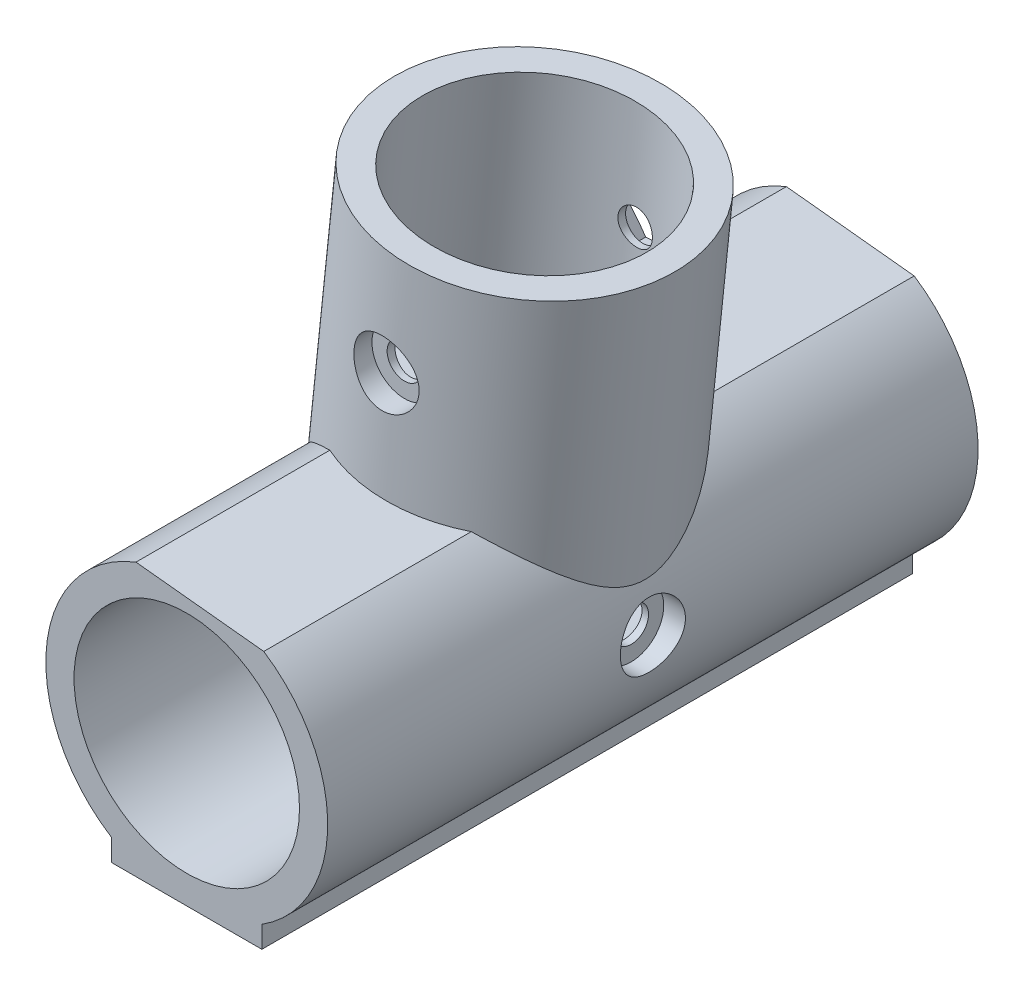
SolidWorks part; units mm, degrees
ref_plane "Front Plane" through (0, 0, 0) normal (0, 0, 1) x (1, 0, 0)
ref_plane "Top Plane" through (0, 0, 0) normal (0, 1, 0) x (1, 0, 0)
ref_plane "Right Plane" through (0, 0, 0) normal (1, 0, 0) x (0, 0, -1)
sketch "Sketch1" plane through (0, 0, 0) normal (0, 0, 1) x (1, 0, 0)
  line L0 (-13, 13) -> (13, -13) construction
  line L1 (-13, 13) -> (13, 13)
  line L2 (-13, 13) -> (-13, -13)
  line L3 (-13, -13) -> (13, -13)
  line L4 (13, 13) -> (13, -13)
  circle A0 centre (0, 0) radius 10.4
  point P4 (0, 0)
  dimension "D2" = 20.8
  dimension "D1" = 26
extrude "Boss-Extrude2" add sketch "Sketch1" along normal blind 60
sketch "Sketch2" plane through (-13, 0, 0) normal (-1, 0, 0) x (0, 0, 1)
  line L0 (0, 13) -> (60, -13) construction
  circle A0 centre (30, 0) radius 1.6
  point P4 (30, 0)
  dimension "D1" = 3.2
extrude "Cut-Extrude1" cut sketch "Sketch2" against normal through all
sketch "Sketch3" plane through (-13, 0, 0) normal (-1, 0, 0) x (0, 0, 1)
  line L1 (33.3486, 0) -> (31.6743, 2.9)
  line L2 (31.6743, 2.9) -> (28.3257, 2.9)
  line L3 (28.3257, 2.9) -> (26.6514, 0)
  line L4 (26.6514, 0) -> (28.3257, -2.9)
  line L5 (28.3257, -2.9) -> (31.6743, -2.9)
  line L6 (31.6743, -2.9) -> (33.3486, 0)
  circle A0 centre (30, 0) radius 2.9 construction
  dimension "D1" = 5.8
extrude "Cut-Extrude2" cut sketch "Sketch3" against normal blind 2
sketch "Sketch4" plane through (13, 0, 0) normal (1, 0, 0) x (0, 0, -1)
  circle A0 centre (-30, 0) radius 3
  dimension "D1" = 6
extrude "Cut-Extrude3" cut sketch "Sketch4" against normal blind 2
sketch "Sketch6" plane through (0, 0, 60) normal (0, 0, 1) x (1, 0, 0)
  line L0 (-13, 13) -> (13, 13)
  line L1 (13, 13) -> (13, 10.2673)
  line L2 (13, -13) -> (13, 13) construction
  line L3 (13, 10.2673) -> (-13, 13)
  dimension "D1" = 6
extrude "Cut-Extrude5" cut sketch "Sketch6" against normal through all
sketch "Sketch7" plane through (1.2094, 11.5065, 0) normal (0.1045, 0.9945, 0) x (0.9945, -0.1045, 0)
  line L0 (-14.2877, 0) -> (11.8556, -60) construction
  line L1 (-14.216, -17) -> (11.784, -43) construction
  line L2 (-14.216, -17) -> (11.784, -17)
  line L3 (-14.216, -17) -> (-14.216, -43)
  line L4 (-14.216, -43) -> (11.784, -43)
  line L5 (11.784, -17) -> (11.784, -43)
  line L6 (-1.216, -30) -> (-14.2877, -30) construction
  line L7 (-14.2877, -60) -> (-14.2877, 0) construction
  point P8 (-1.216, -30)
  dimension "D1" = 26
extrude "Boss-Extrude3" add sketch "Sketch7" along normal blind 20
sketch "Sketch8" plane through (0, 0, 43) normal (0, 0, 1) x (1, 0, 0)
  line L0 (-10.8382, 32.883) -> (13, 10.2673) construction
  circle A0 centre (1.0809, 21.5751) radius 1.6
  dimension "D1" = 3.2
extrude "Cut-Extrude6" cut sketch "Sketch8" against normal through all
sketch "Sketch9" plane through (0, 0, 43) normal (0, 0, 1) x (1, 0, 0)
  line L0 (-0.5191, 21.5751) -> (1.0809, 21.5751) construction
  circle A0 centre (1.0809, 21.5751) radius 1.6 construction
  circle A1 centre (1.0809, 21.5751) radius 3
  dimension "D1" = 6
extrude "Cut-Extrude7" cut sketch "Sketch9" against normal blind 2
sketch "Sketch10" plane through (0, 0, 17) normal (0, 0, -1) x (-1, 0, 0)
  line L1 (2.2677, 21.5751) -> (0.5934, 24.4751)
  line L2 (0.5934, 24.4751) -> (-2.7552, 24.4751)
  line L3 (-2.7552, 24.4751) -> (-4.4295, 21.5751)
  line L4 (-4.4295, 21.5751) -> (-2.7552, 18.6751)
  line L5 (-2.7552, 18.6751) -> (0.5934, 18.6751)
  line L6 (0.5934, 18.6751) -> (2.2677, 21.5751)
  circle A0 centre (-1.0809, 21.5751) radius 2.9 construction
  dimension "D1" = 5.8
extrude "Cut-Extrude8" cut sketch "Sketch10" against normal blind 2
sketch "Sketch11" plane through (3.3, 31.397, 0) normal (0.1045, 0.9945, 0) x (0.9945, -0.1045, 0)
  line L0 (-14.216, -43) -> (11.784, -17) construction
  circle A0 centre (-1.216, -30) radius 10.4
  circle A1 centre (-1.216, -30) radius 13
  dimension "D1" = 26
  dimension "D2" = 20.8
extrude "Cut-Extrude9" cut sketch "Sketch11" against normal blind 20 flip side to cut
sketch "Sketch5" plane through (0, 0, 60) normal (0, 0, 1) x (1, 0, 0)
  line L0 (0, -13) -> (0, -11) construction
  line L2 (-6.9282, -11) -> (6.9282, -11) construction
  line L3 (-6.9282, -11) -> (-6.9282, -13)
  line L4 (-13, -13) -> (13, -13) construction
  line L5 (-6.9282, -13) -> (6.9282, -13)
  line L6 (6.9282, -13) -> (6.9282, -11)
  line L7 (-13, 13) -> (-4.6858, 12.1261)
  line L8 (13, 10.2673) -> (15.2917, 31.8314)
  line L9 (15.2917, 31.8314) -> (-10.7083, 34.5945)
  line L10 (-10.7083, 34.5945) -> (-13, 13)
  line L11 (7.1046, 10.8869) -> (13, 10.2673)
  arc A0 (6.9282, -11) -> (7.1046, 10.8869) centre (0, 0) ccw
  arc A1 (-4.6858, 12.1261) -> (-6.9282, -11) centre (0, 0) ccw
  point P5 (0, -11)
  dimension "D2" = 26
  dimension "D1" = 2
  dimension "D3" = 26
extrude "Cut-Extrude4" cut sketch "Sketch5" against normal through all flip side to cut
sketch "Sketch13" plane through (1.2094, 11.5065, 0) normal (-0.1045, -0.9945, 0) x (0.9945, -0.1045, 0)
  line L0 (-14.216, 30) -> (-1.216, 30) construction
  arc A0 (-5.9277, 42.1161) -> (-5.9277, 17.8839) centre (-1.216, 30) ccw construction
  circle A2 centre (-1.216, 30) radius 13
  dimension "D2" = 26
  dimension "D1" = 13
extrude "Boss-Extrude4" add sketch "Sketch13" along normal blind 7
fillet "Fillet1" radius 2 1 edges at (-11.6259, 5.817, 30)
sketch "Sketch14" plane through (0, 0, 60) normal (0, 0, 1) x (1, 0, 0)
  circle A0 centre (0, 0) radius 10.4
extrude "Cut-Extrude10" cut sketch "Sketch14" against normal through all
